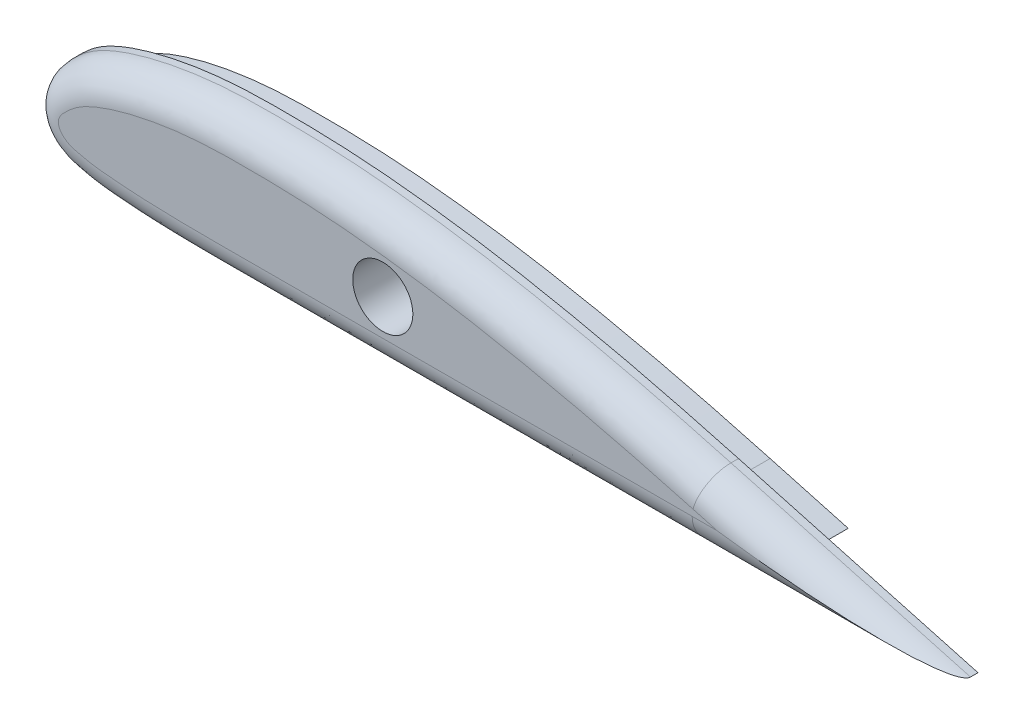
SolidWorks part; units mm, degrees
ref_plane "Front Plane" through (0, 0, 0) normal (0, 0, 1) x (1, 0, 0)
ref_plane "Top Plane" through (0, 0, 0) normal (0, 1, 0) x (1, 0, 0)
ref_plane "Right Plane" through (0, 0, 0) normal (1, 0, 0) x (0, 0, -1)
sketch "Sketch1" plane through (0, 0, 0) normal (0, 0, 1) x (1, 0, 0)
  line L4 (441.3938, 20.1125) -> (474.4331, 20.1125)
  line L5 (474.4331, 20.1125) -> (442.557, 28.8563)
  spline S2 degree 3 poles (442.557, 28.8563) (439.0727, 29.8121) (432.0999, 31.6716) (421.4868, 34.1106) (410.7798, 36.1975) (401.7202, 37.4887) (394.4128, 38.2045) (388.8653, 38.5359) (383.377, 38.6454) (378.7767, 38.631) (374.9635, 38.4319) (372.0662, 38.14) (369.2107, 37.707) (366.8278, 37.2314) (364.9084, 36.7539) (363.4799, 36.3495) (362.0564, 35.8958) (360.5728, 35.3529) (359.2877, 34.7841) (358.2164, 34.2146) (357.3891, 33.7069) (356.5526, 33.1031) (355.8208, 32.4753) (355.3545, 32.0442) (354.8557, 31.5528) (354.39, 31.0256) (353.965, 30.4492) (353.5863, 29.7672) (353.2277, 28.9329) (352.9613, 27.6499) (353.1116, 26.2983) (353.3653, 25.4506) (353.6956, 24.7529) (353.9982, 24.2624) (354.3478, 23.793) (354.7889, 23.3017) (355.3251, 22.8111) (356.056, 22.2868) (356.8397, 21.8718) (357.7655, 21.5068) (358.6401, 21.281) (359.288, 21.1303) (360.0698, 20.9562) (360.9049, 20.8056) (361.9719, 20.652) (363.214, 20.5264) (364.5787, 20.4101) (365.9782, 20.3046) (367.3787, 20.22) (369.229, 20.1314) (371.5307, 20.0564) (374.2712, 20.0109) (376.991, 19.9944) (379.6961, 19.9964) (383.2749, 20.0094) (387.735, 20.0177) (393.1045, 20.0244) (398.4705, 20.035) (403.8355, 20.0448) (410.9894, 20.058) (419.9315, 20.0736) (430.6622, 20.0933) (437.8166, 20.1056) (441.3938, 20.1125) knots 0 0 0 0 0.062498 0.124997 0.187495 0.249994 0.281243 0.312492 0.343742 0.374991 0.390615 0.40624 0.421865 0.437489 0.445302 0.453114 0.460926 0.468739 0.476551 0.480457 0.484363 0.488269 0.492175 0.496082 0.498035 0.499988 0.501941 0.502917 0.503894 0.505847 0.506824 0.5078 0.508777 0.509753 0.51073 0.511706 0.513659 0.515612 0.517566 0.519519 0.523425 0.527331 0.531237 0.535143 0.539049 0.546862 0.554674 0.562486 0.570299 0.578111 0.593736 0.60936 0.624985 0.640609 0.656234 0.687483 0.718732 0.749982 0.781231 0.81248 0.874979 0.937477 0.999976 0.999976 0.999976 0.999976
extrude "Boss-Extrude1" add sketch "Sketch1" along normal blind 10
fillet "Fillet1" radius 4 3 edges at (458.4951, 24.4844, 10) (457.9135, 20.1125, 10)
sketch "Sketch2" plane through (0, 0, 0) normal (0, 0, -1) x (-1, 0, 0)
  line L4 (-441.7634, 25.9631) -> (-452.1558, 23.1125)
  line L5 (-452.1558, 23.1125) -> (-441.3909, 23.1125)
  line L6 (-441.7634, 25.9631) -> (-452.1558, 23.1125)
  line L7 (-452.1558, 23.1125) -> (-441.3909, 23.1125)
  line L8 (-442.557, 28.8563) -> (-474.4331, 20.1125)
  line L9 (-474.4331, 20.1125) -> (-441.3938, 20.1125)
  line L10 (-442.557, 28.8563) -> (-474.4331, 20.1125)
  line L11 (-474.4331, 20.1125) -> (-441.3938, 20.1125)
  spline S2 degree 3 poles (-2884.3924, 1450.6573) (-2054.7336, 13.0638) (-1225.8234, 24.6115) (-393.1993, 23.0248) (-389.4923, 23.0208) (-383.9317, 23.0103) (-382.0782, 23.004) (-378.3711, 22.994) (-376.5176, 22.9932) (-372.8106, 23.0302) (-370.9571, 23.0679) (-368.1769, 23.1826) (-367.2509, 23.2302) (-365.4019, 23.3528) (-364.4785, 23.4259) (-363.0954, 23.554) (-362.6347, 23.6) (-361.7158, 23.7166) (-361.2575, 23.7874) (-360.5728, 23.9195) (-360.3451, 23.9686) (-359.89, 24.0707) (-359.6626, 24.123) (-359.21, 24.2333) (-358.984, 24.2896) (-358.5407, 24.4283) (-358.3225, 24.5084) (-357.8979, 24.7039) (-357.6895, 24.8196) (-357.3031, 25.0852) (-357.1213, 25.2328) (-356.8687, 25.4799) (-356.787, 25.566) (-356.6356, 25.7449) (-356.5657, 25.8382) (-356.3677, 26.1258) (-356.2583, 26.3349) (-356.0952, 26.7786) (-356.0486, 27.0088) (-356.0238, 27.4825) (-356.0548, 27.7144) (-356.1384, 28.0581) (-356.1729, 28.171) (-356.2602, 28.3875) (-356.3123, 28.4921) (-356.4256, 28.6971) (-356.4874, 28.7979) (-356.6194, 28.9904) (-356.6904, 29.082) (-356.9102, 29.3509) (-357.0677, 29.5202) (-357.3981, 29.8448) (-357.5667, 30.0039) (-357.9121, 30.3148) (-358.0871, 30.4672) (-358.4445, 30.7599) (-358.6278, 30.8992) (-359.19, 31.2975) (-359.5817, 31.5368) (-360.3915, 31.9741) (-360.81, 32.1743) (-362.0831, 32.7267) (-362.948, 33.031) (-364.6922, 33.5823) (-365.5719, 33.8275) (-367.3449, 34.2644) (-368.2385, 34.4546) (-370.0371, 34.79) (-370.9417, 34.9368) (-372.7619, 35.1863) (-373.6759, 35.2883) (-375.4974, 35.4473) (-376.4069, 35.5036) (-379.1328, 35.623) (-380.9467, 35.6387) (-384.5717, 35.6183) (-386.3832, 35.5876) (-390.0024, 35.4577) (-391.81, 35.3569) (-395.4218, 35.0866) (-397.2258, 34.9163) (-402.6333, 34.3225) (-406.2327, 33.8193) (-413.4213, 32.623) (-416.9976, 31.9312) (-424.1193, 30.4262) (-427.6665, 29.6139) (-587.2549, -9.896) (-715.1223, -171.9625) (-1555.7127, 2786.8732) knots -13.725361 -13.725361 -13.725361 -13.725361 0.25 0.25 0.3125 0.3125 0.34375 0.34375 0.375 0.375 0.40625 0.40625 0.421875 0.421875 0.4375 0.4375 0.445313 0.445313 0.453125 0.453125 0.457031 0.457031 0.460938 0.460938 0.464844 0.464844 0.46875 0.46875 0.472656 0.472656 0.476563 0.476563 0.478516 0.478516 0.480469 0.480469 0.484375 0.484375 0.488281 0.488281 0.492188 0.492188 0.494141 0.494141 0.496094 0.496094 0.498047 0.498047 0.5 0.5 0.503906 0.503906 0.507813 0.507813 0.511719 0.511719 0.515625 0.515625 0.523438 0.523438 0.53125 0.53125 0.546875 0.546875 0.5625 0.5625 0.578125 0.578125 0.59375 0.59375 0.609375 0.609375 0.625 0.625 0.65625 0.65625 0.6875 0.6875 0.71875 0.71875 0.75 0.75 0.8125 0.8125 0.875 0.875 0.9375 0.9375 3.698228 3.698228 3.698228 3.698228 only from (-441.3909, 23.1125) to (-441.7634, 25.9631)
  spline S3 degree 3 poles (-441.3909, 23.1125) (-426.5627, 23.0842) (-411.7345, 23.0602) (-393.1993, 23.0248) (-389.4923, 23.0208) (-383.9317, 23.0103) (-382.0782, 23.004) (-378.3711, 22.994) (-376.5176, 22.9932) (-372.8106, 23.0302) (-370.9571, 23.0679) (-368.1769, 23.1826) (-367.2509, 23.2302) (-365.4019, 23.3528) (-364.4785, 23.4259) (-363.0954, 23.554) (-362.6347, 23.6) (-361.7158, 23.7166) (-361.2575, 23.7874) (-360.5728, 23.9195) (-360.3451, 23.9686) (-359.89, 24.0707) (-359.6626, 24.123) (-359.21, 24.2333) (-358.984, 24.2896) (-358.5407, 24.4283) (-358.3225, 24.5084) (-357.8979, 24.7039) (-357.6895, 24.8196) (-357.3031, 25.0852) (-357.1213, 25.2328) (-356.8687, 25.4799) (-356.787, 25.566) (-356.6356, 25.7449) (-356.5657, 25.8382) (-356.3677, 26.1258) (-356.2583, 26.3349) (-356.0952, 26.7786) (-356.0486, 27.0088) (-356.0238, 27.4825) (-356.0548, 27.7144) (-356.1384, 28.0581) (-356.1729, 28.171) (-356.2602, 28.3875) (-356.3123, 28.4921) (-356.4256, 28.6971) (-356.4874, 28.7979) (-356.6194, 28.9904) (-356.6904, 29.082) (-356.9102, 29.3509) (-357.0677, 29.5202) (-357.3981, 29.8448) (-357.5667, 30.0039) (-357.9121, 30.3148) (-358.0871, 30.4672) (-358.4445, 30.7599) (-358.6278, 30.8992) (-359.19, 31.2975) (-359.5817, 31.5368) (-360.3915, 31.9741) (-360.81, 32.1743) (-362.0831, 32.7267) (-362.948, 33.031) (-364.6922, 33.5823) (-365.5719, 33.8275) (-367.3449, 34.2644) (-368.2385, 34.4546) (-370.0371, 34.79) (-370.9417, 34.9368) (-372.7619, 35.1863) (-373.6759, 35.2883) (-375.4974, 35.4473) (-376.4069, 35.5036) (-379.1328, 35.623) (-380.9467, 35.6387) (-384.5717, 35.6183) (-386.3832, 35.5876) (-390.0024, 35.4577) (-391.81, 35.3569) (-395.4218, 35.0866) (-397.2258, 34.9163) (-402.6333, 34.3225) (-406.2327, 33.8193) (-413.4213, 32.623) (-416.9976, 31.9312) (-424.1193, 30.4262) (-427.6665, 29.6139) (-434.7323, 27.8646) (-438.2508, 26.9267) (-441.7634, 25.9631) knots 0 0 0 0 0.25 0.25 0.3125 0.3125 0.34375 0.34375 0.375 0.375 0.40625 0.40625 0.421875 0.421875 0.4375 0.4375 0.445313 0.445313 0.453125 0.453125 0.457031 0.457031 0.460938 0.460938 0.464844 0.464844 0.46875 0.46875 0.472656 0.472656 0.476563 0.476563 0.478516 0.478516 0.480469 0.480469 0.484375 0.484375 0.488281 0.488281 0.492188 0.492188 0.494141 0.494141 0.496094 0.496094 0.498047 0.498047 0.5 0.5 0.503906 0.503906 0.507813 0.507813 0.511719 0.511719 0.515625 0.515625 0.523438 0.523438 0.53125 0.53125 0.546875 0.546875 0.5625 0.5625 0.578125 0.578125 0.59375 0.59375 0.609375 0.609375 0.625 0.625 0.65625 0.65625 0.6875 0.6875 0.71875 0.71875 0.75 0.75 0.8125 0.8125 0.875 0.875 0.9375 0.9375 1 1 1 1
  spline S4 degree 3 poles (-1244.353, 2624.291) (-1501.2387, 18.1594) (-960.5746, 21.0619) (-419.9315, 20.0736) (-410.9894, 20.058) (-403.8355, 20.0448) (-398.4705, 20.035) (-393.1045, 20.0244) (-387.735, 20.0177) (-383.2749, 20.0094) (-379.6961, 19.9964) (-376.991, 19.9944) (-374.2712, 20.0109) (-371.5307, 20.0564) (-369.229, 20.1314) (-367.3787, 20.22) (-365.9782, 20.3046) (-364.5787, 20.4101) (-363.214, 20.5264) (-361.9719, 20.652) (-360.9049, 20.8056) (-360.0698, 20.9562) (-359.288, 21.1303) (-358.6401, 21.281) (-357.7655, 21.5068) (-356.8397, 21.8718) (-356.056, 22.2868) (-355.3251, 22.8111) (-354.7889, 23.3017) (-354.3478, 23.793) (-353.9982, 24.2624) (-353.6956, 24.7529) (-353.3653, 25.4506) (-353.1116, 26.2983) (-352.9613, 27.6499) (-353.2277, 28.9329) (-353.5863, 29.7672) (-353.965, 30.4492) (-354.39, 31.0256) (-354.8557, 31.5528) (-355.3545, 32.0442) (-355.8208, 32.4753) (-356.5526, 33.1031) (-357.3891, 33.7069) (-358.2164, 34.2146) (-359.2877, 34.7841) (-360.5728, 35.3529) (-362.0564, 35.8958) (-363.4799, 36.3495) (-364.9084, 36.7539) (-366.8278, 37.2314) (-369.2107, 37.707) (-372.0662, 38.14) (-374.9635, 38.4319) (-378.7767, 38.631) (-383.377, 38.6454) (-388.8653, 38.5359) (-394.4128, 38.2045) (-401.7202, 37.4887) (-410.7798, 36.1975) (-421.4868, 34.1106) (-579.4195, -2.1837) (-684.9381, -148.8712) (-2575.8753, 2111.064) knots -9.259048 -9.259048 -9.259048 -9.259048 0.062498 0.124997 0.187495 0.218745 0.249994 0.281243 0.312492 0.343742 0.359366 0.374991 0.390615 0.40624 0.421865 0.429677 0.437489 0.445302 0.453114 0.460926 0.464832 0.468739 0.472645 0.476551 0.480457 0.48241 0.484363 0.486316 0.488269 0.489246 0.490222 0.491199 0.492175 0.493152 0.494129 0.496082 0.497058 0.498035 0.499988 0.501941 0.503894 0.5078 0.511706 0.515612 0.519519 0.523425 0.531237 0.539049 0.546862 0.554674 0.562486 0.578111 0.593736 0.60936 0.624985 0.656234 0.687483 0.718732 0.749982 0.81248 0.874979 0.937477 3.602583 3.602583 3.602583 3.602583 only from (-441.3938, 20.1125) to (-442.557, 28.8563)
  spline S5 degree 3 poles (-441.3938, 20.1125) (-437.8166, 20.1056) (-430.6622, 20.0933) (-419.9315, 20.0736) (-410.9894, 20.058) (-403.8355, 20.0448) (-398.4705, 20.035) (-393.1045, 20.0244) (-387.735, 20.0177) (-383.2749, 20.0094) (-379.6961, 19.9964) (-376.991, 19.9944) (-374.2712, 20.0109) (-371.5307, 20.0564) (-369.229, 20.1314) (-367.3787, 20.22) (-365.9782, 20.3046) (-364.5787, 20.4101) (-363.214, 20.5264) (-361.9719, 20.652) (-360.9049, 20.8056) (-360.0698, 20.9562) (-359.288, 21.1303) (-358.6401, 21.281) (-357.7655, 21.5068) (-356.8397, 21.8718) (-356.056, 22.2868) (-355.3251, 22.8111) (-354.7889, 23.3017) (-354.3478, 23.793) (-353.9982, 24.2624) (-353.6956, 24.7529) (-353.3653, 25.4506) (-353.1116, 26.2983) (-352.9613, 27.6499) (-353.2277, 28.9329) (-353.5863, 29.7672) (-353.965, 30.4492) (-354.39, 31.0256) (-354.8557, 31.5528) (-355.3545, 32.0442) (-355.8208, 32.4753) (-356.5526, 33.1031) (-357.3891, 33.7069) (-358.2164, 34.2146) (-359.2877, 34.7841) (-360.5728, 35.3529) (-362.0564, 35.8958) (-363.4799, 36.3495) (-364.9084, 36.7539) (-366.8278, 37.2314) (-369.2107, 37.707) (-372.0662, 38.14) (-374.9635, 38.4319) (-378.7767, 38.631) (-383.377, 38.6454) (-388.8653, 38.5359) (-394.4128, 38.2045) (-401.7202, 37.4887) (-410.7798, 36.1975) (-421.4868, 34.1106) (-432.0999, 31.6716) (-439.0727, 29.8121) (-442.557, 28.8563) knots 0 0 0 0 0.062498 0.124997 0.187495 0.218745 0.249994 0.281243 0.312492 0.343742 0.359366 0.374991 0.390615 0.40624 0.421865 0.429677 0.437489 0.445302 0.453114 0.460926 0.464832 0.468739 0.472645 0.476551 0.480457 0.48241 0.484363 0.486316 0.488269 0.489246 0.490222 0.491199 0.492175 0.493152 0.494129 0.496082 0.497058 0.498035 0.499988 0.501941 0.503894 0.5078 0.511706 0.515612 0.519519 0.523425 0.531237 0.539049 0.546862 0.554674 0.562486 0.578111 0.593736 0.60936 0.624985 0.656234 0.687483 0.718732 0.749982 0.81248 0.874979 0.937477 0.999976 0.999976 0.999976 0.999976
  dimension "D1" = 3
  dimension "D2" = 0
extrude "Cut-Extrude1" cut sketch "Sketch2" against normal blind 5
sketch "Sketch3" plane through (0, 0, 10) normal (0, 0, 1) x (1, 0, 0)
  line L0 (391.0992, 24.4198) -> (409.3338, 24.4198) construction
  line L1 (391.0992, 24.4198) -> (409.3338, 24.4198) construction
  line L2 (389.0992, 31.2372) -> (389.0992, 26.4198) construction
  line L3 (389.0992, 31.2372) -> (389.0992, 26.4198) construction
  line L4 (389.0992, 28.8285) -> (400.2165, 28.8285) construction
  line L5 (400.2165, 28.8285) -> (400.2165, 24.4198) construction
  circle A0 centre (400.2165, 28.8285) radius 4
extrude "Cut-Extrude2" cut sketch "Sketch3" against normal through all
